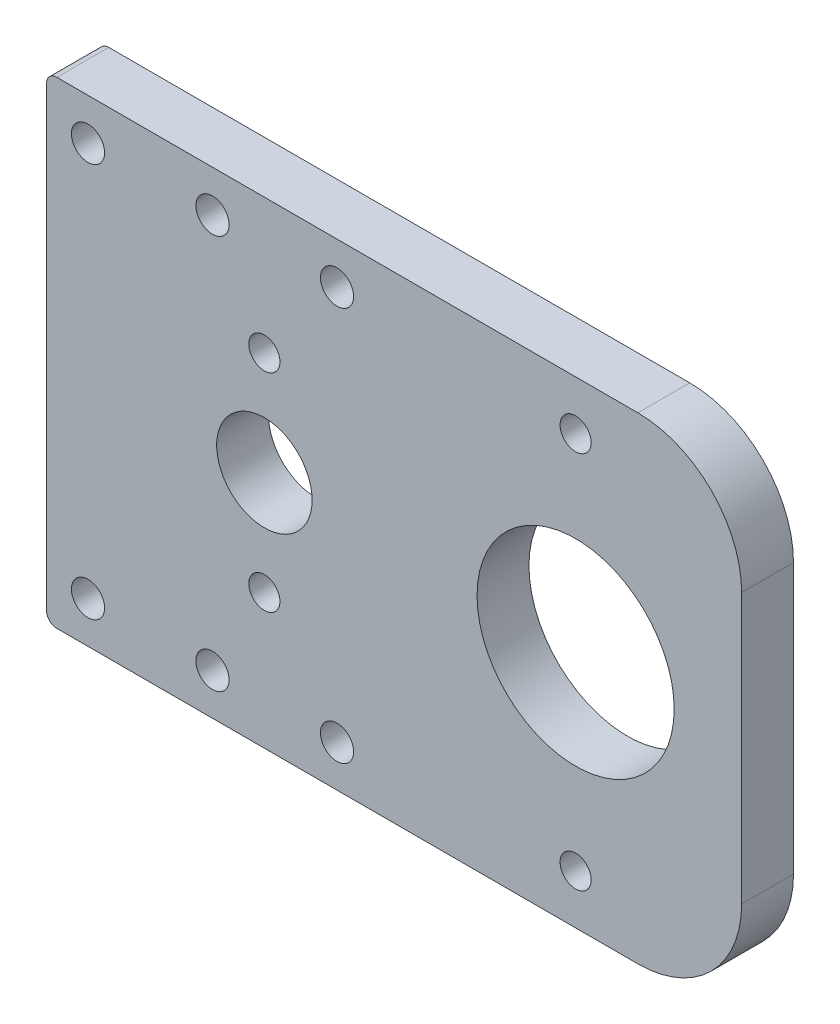
SolidWorks part; units mm, degrees
material "Acrylic (Medium-high impact)"
ref_plane "Front Plane" through (0, 0, 0) normal (0, 0, 1) x (1, 0, 0)
ref_plane "Top Plane" through (0, 0, 0) normal (0, 1, 0) x (1, 0, 0)
ref_plane "Right Plane" through (0, 0, 0) normal (1, 0, 0) x (0, 0, -1)
sketch "Sketch1" plane through (0, 0, 0) normal (0, 0, 1) x (1, 0, 0)
  line L0 (-25.3491, 0) -> (24.7222, 0) construction
  line L1 (40, -23) -> (-40, -23)
  line L2 (40, -23) -> (40, 23)
  line L3 (40, 23) -> (-40, 23)
  line L4 (-40, -23) -> (-40, 23)
  line L5 (40, -23) -> (-40, 23) construction
  line L6 (40, 23) -> (-40, -23) construction
  line L7 (30, 0) -> (30, 18.25)
  line L8 (-40, 23) -> (-25, 23)
  line L9 (-25, 23) -> (-25, -23)
  line L10 (0, 0) -> (0, -10)
  circle A0 centre (0, 0) radius 4.6
  circle A1 centre (30, 0) radius 9.5
  circle A2 centre (30, 18.25) radius 1.5
  circle A3 centre (30, -18.25) radius 1.5
  circle A4 centre (0, -10) radius 1.5
  circle A5 centre (0, 10) radius 1.5
  point P0 (0, 0)
  dimension "D1" = 9.2
  dimension "D2" = 19
  dimension "D7" = 3
  dimension "D10" = 3
  dimension "D3" = 46
  dimension "D4" = 30
  dimension "D5" = 80
  dimension "D6" = 18.25
  dimension "D8" = 15
  dimension "D9" = 10
extrude "Boss-Extrude1" add sketch "Sketch1" along normal blind 5 contours L4 L1 L2 L3 A0 A2 A1 A3 region at (5.1671, 0, 0)
sketch "Sketch2" plane through (0, 0, 5) normal (0, 0, 1) x (1, 0, 0)
  line L0 (-25, -23) -> (-25, 23)
  line L1 (-25, -23) -> (-5, -23)
  line L2 (-25, 23) -> (-5, 23)
  line L3 (-5, -23) -> (-5, 23)
  line L4 (-25, 23) -> (-25, -23)
  line L5 (-25, -23) -> (40, -23)
  line L6 (40, -23) -> (40, 23)
  line L7 (40, 23) -> (-25, 23)
  line L9 (-25, -23) -> (40, -23)
  line L10 (40, -23) -> (40, 23)
  line L11 (40, 23) -> (-25, 23)
  line L12 (-17, 19) -> (-25, 19)
  line L13 (-17, 19) -> (-5, 19)
  line L14 (-5, 19) -> (7, 19)
  line L16 (-5, 0) -> (-25, 0)
  line L20 (-25, 23) -> (-25, -23)
  circle A0 centre (-17, 19) radius 1.6
  circle A1 centre (-5, 19) radius 1.6
  circle A5 centre (7, 19) radius 1.6
  circle A6 centre (7, -19) radius 1.6
  circle A7 centre (-5, -19) radius 1.6
  circle A8 centre (-17, -19) radius 1.6
  dimension "D5" = 3.2
  dimension "D6" = 3.2
  dimension "D7" = 19
  dimension "D8" = 3.2
  dimension "D2" = 20
  dimension "D3" = 12
  dimension "D4" = 12
  dimension "D9" = 8
  dimension "D1" = 0
extrude "Cut-Extrude1" cut sketch "Sketch2" against normal blind 10 contours A8 | A7 L3 | A7 L3 | A6 | A5 | L14 A1 L3 | L3 A1 L13 | L13 A1 L3 | L3 A1 L14 | L13 A0 L12 | L12 A0 L13 region at (7, 20.5547, 5) region at (-5.6791, -19, 5) region at (-4.3209, -19, 5) region at (-17, 19.6791, 5) region at (-17, 18.3209, 5) region at (-5.6791, 18.3209, 5) region at (-4.3209, 18.3209, 5) region at (-5.6791, 19.6791, 5) region at (-4.3209, 19.6791, 5) region at (7, -19, 5) region at (-17, -19, 5)
sketch "Sketch3" plane through (0, 0, 5) normal (0, 0, 1) x (1, 0, 0)
  line L0 (-25, 23) -> (-21, 23)
  line L1 (-21, 23) -> (-21, -23)
  line L4 (40, 23) -> (-25, 23)
  line L5 (-25, 23) -> (-25, -23)
  line L6 (-25, -23) -> (40, -23)
  line L7 (40, -23) -> (40, 23)
  line L8 (40, 23) -> (-25, 23)
  line L9 (-25, 23) -> (-25, -23)
  line L10 (-25, -23) -> (40, -23)
  line L11 (40, -23) -> (40, 23)
  line M10 (40, 23) -> (-25, 23)
  line M11 (-25, 23) -> (-25, -23)
  line M12 (-25, -23) -> (40, -23)
  dimension "D2" = 4
  dimension "D1" = 0
extrude "Cut-Extrude2" cut sketch "Sketch3" against normal through all contours L1 M10 M11 M12 region at (-23, 0, 5)
sketch "Sketch4" plane through (0, 0, 5) normal (0, 0, 1) x (1, 0, 0)
  line L1 (40, 23) -> (46, 23)
  line L2 (40, 23) -> (40, -23)
  line L3 (40, -23) -> (46, -23)
  line L4 (40, 23) -> (-21, 23)
  line L5 (-21, 23) -> (-21, -23)
  line L6 (-21, -23) -> (40, -23)
  line L7 (40, -23) -> (40, 23)
  line L8 (40, 23) -> (-21, 23)
  line L9 (-21, 23) -> (-21, -23)
  line L10 (-21, -23) -> (40, -23)
  line L11 (40, -23) -> (40, 23)
  line L12 (46, 23) -> (46, -23)
  line M19 (40, -23) -> (40, 23)
  dimension "D2" = 6
  dimension "D1" = 0
extrude "Boss-Extrude2" add sketch "Sketch4" against normal up to surface (5 mm away) contours L12 L1 L3 M19 region at (43, 0, 5) up to face at (-15.4, 19, 0)
fillet "Fillet1" radius 10 2 edges at (46, 23, 2.5) (46, -23, 2.5)
fillet "Fillet2" radius 1 2 edges at (-21, 23, 2.5) (-21, -23, 2.5)
